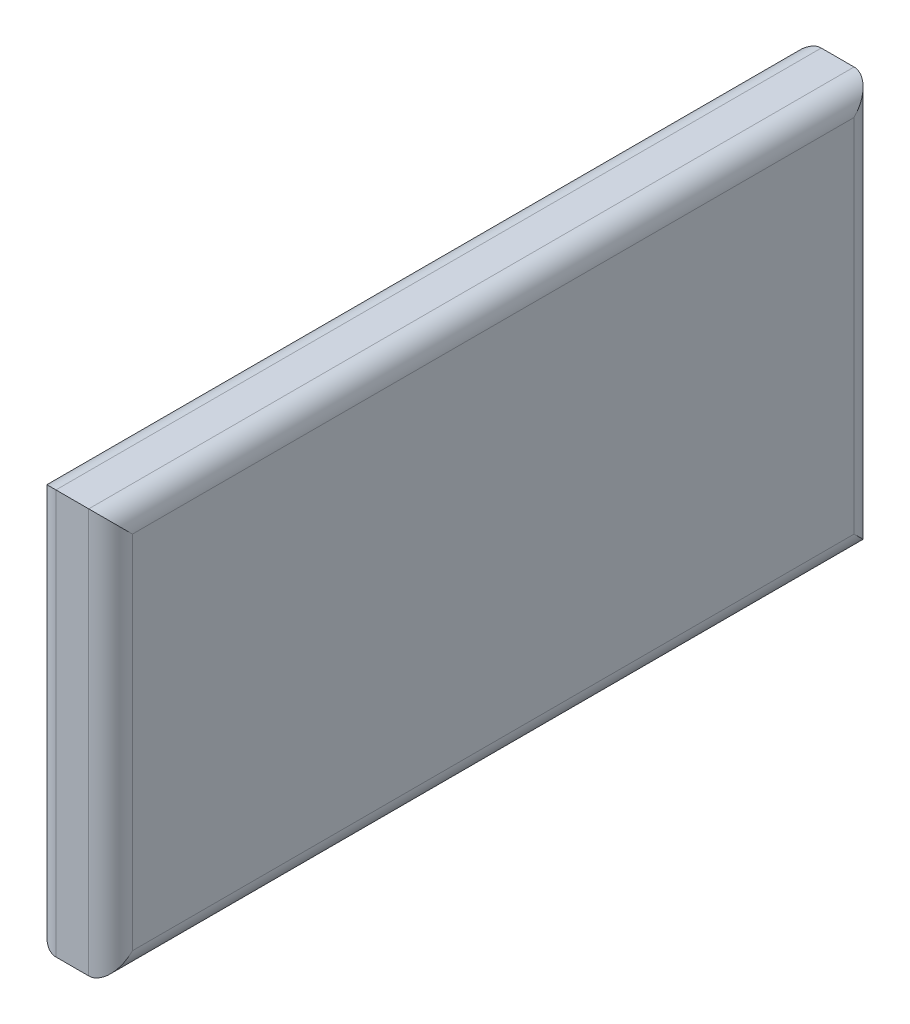
SolidWorks part; units mm, degrees
material "C (Graphite)"
ref_plane "Front" through (0, 0, 0) normal (0, 0, 1) x (1, 0, 0)
ref_plane "Top" through (0, 0, 0) normal (0, 1, 0) x (1, 0, 0)
ref_plane "Right" through (0, 0, 0) normal (1, 0, 0) x (0, 0, -1)
sketch "Sketch1" plane through (0, 0, 0) normal (1, 0, 0) x (0, 0, -1)
  line L1 (0, 0) -> (70, 0)
  line L2 (0, 0) -> (0, 37)
  line L3 (0, 37) -> (70, 37)
  line L4 (70, 0) -> (70, 37)
  dimension "D1" = 70
  dimension "D2" = 37
extrude "Boss-Extrude1" add sketch "Sketch1" along normal blind 7
fillet "Fillet1" radius 2 8 edges at (0, 18.5, 0) (7, 18.5, 0) (7, 18.5, -70) (0, 18.5, -70) (7, 0, -35) (7, 37, -35) (0, 37, -35) (0, 0, -35)
